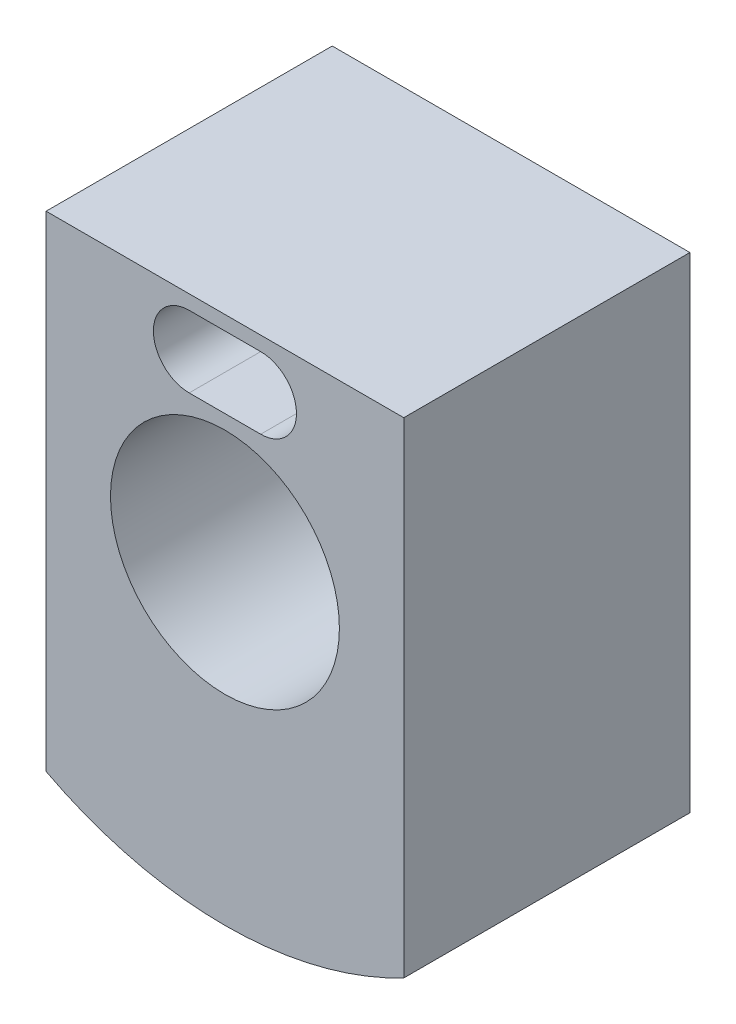
SolidWorks part; units mm, degrees
ref_plane "Front Plane" through (0, 0, 0) normal (0, 0, 1) x (1, 0, 0)
ref_plane "Top Plane" through (0, 0, 0) normal (0, 1, 0) x (1, 0, 0)
ref_plane "Right Plane" through (0, 0, 0) normal (1, 0, 0) x (0, 0, -1)
sketch "Sketch1" plane through (0, 0, 0) normal (0, 0, 1) x (1, 0, 0)
  line L1 (0, 0) -> (0, -53.975) construction
  line L2 (-25, 0) -> (-25, -47.8362)
  line L3 (25, 0) -> (25, -47.8362)
  line L4 (-25, 0) -> (-25, 20)
  line L5 (-25, 20) -> (25, 20)
  line L6 (25, 20) -> (25, 0)
  arc A0 (-25, -47.8362) -> (25, -47.8362) centre (0, 0) ccw
  point P1 (0, 0)
  dimension "D1" = 107.95
  dimension "D2" = 50
  dimension "D3" = 20
extrude "Boss-Extrude2" add sketch "Sketch1" along normal blind 40
sketch "Sketch2" plane through (0, 0, 40) normal (0, 0, 1) x (1, 0, 0)
  line L6 (0, 6) -> (0, -26) construction
  circle A0 centre (0, -10) radius 16
  point P1 (0, 0)
  dimension "D2" = 32
  dimension "D1" = 10
extrude "Cut-Extrude1" cut sketch "Sketch2" against normal through all both
sketch "Sketch4" plane through (0, 0, 40) normal (0, 0, 1) x (1, 0, 0)
  line L0 (-5, 13) -> (5, 13) construction
  line L1 (-5, 18) -> (5, 18)
  line L2 (-5, 8) -> (5, 8)
  line L3 (0, 20) -> (0, 6) construction
  line L4 (25, 20) -> (-25, 20) construction
  arc A0 (-5, 18) -> (-5, 8) centre (-5, 13) ccw
  arc A1 (5, 8) -> (5, 18) centre (5, 13) ccw
  circle A2 centre (0, -10) radius 16 construction
  point P2 (0, 13)
  point P14 (0, 0)
  point P15 (0, 0)
  dimension "D1" = 10
  dimension "D2" = 10
extrude "Cut-Extrude3" cut sketch "Sketch4" against normal through all
